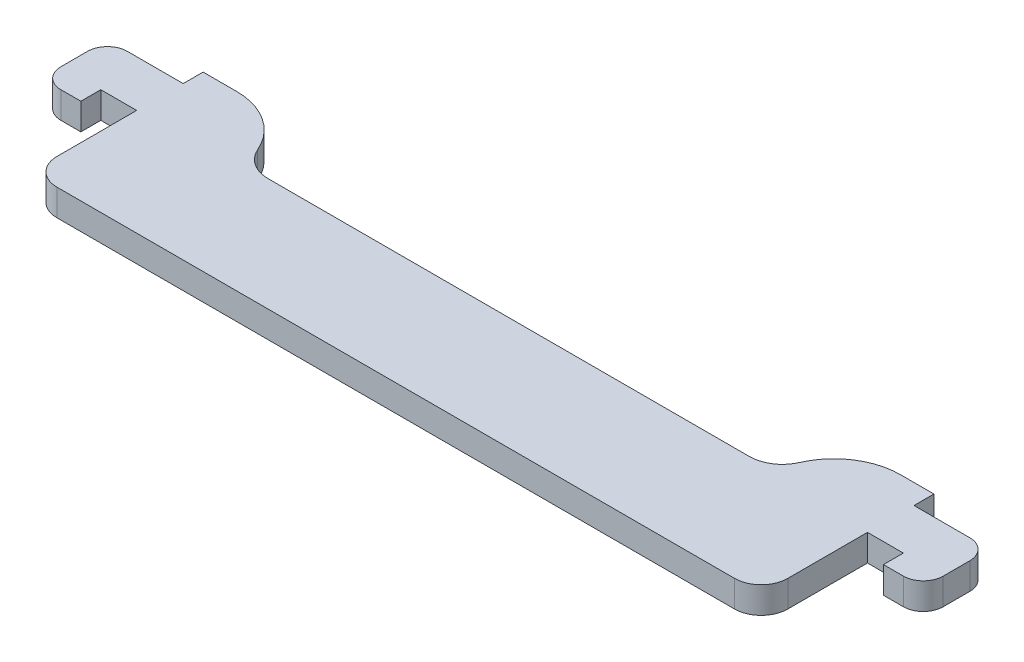
SolidWorks part; units mm, degrees
ref_plane "Piano frontale" through (0, 0, 0) normal (0, 0, 1) x (1, 0, 0)
ref_plane "Piano superiore" through (0, 0, 0) normal (0, 1, 0) x (1, 0, 0)
ref_plane "Piano destro" through (0, 0, 0) normal (1, 0, 0) x (0, 0, -1)
sketch "Schizzo1" plane through (0, 0, 0) normal (0, 1, 0) x (1, 0, 0)
  line L0 (-11.4, 23) -> (-11.4, 13)
  line L1 (-11.4, 13) -> (-5.4, 13)
  line L2 (-5.4, 13) -> (-5.4, 16)
  line L3 (-5.4, 16) -> (0, 16)
  line L4 (0, 16) -> (0, 0)
  line L5 (0, 0) -> (110, 0)
  line L6 (110, 0) -> (110, 16)
  line L7 (110, 16) -> (115.4, 16)
  line L8 (115.4, 16) -> (115.4, 13)
  line L9 (115.4, 13) -> (121.4, 13)
  line L10 (121.4, 13) -> (121.4, 23)
  line L11 (121.4, 23) -> (110, 23)
  line L12 (110, 23) -> (110, 26)
  line L13 (110, 26) -> (95, 26)
  line L14 (95, 26) -> (95, 17)
  line L19 (95, 17) -> (15, 17)
  line L20 (15, 17) -> (15, 26)
  line L21 (15, 26) -> (0, 26)
  line L22 (0, 26) -> (0, 23)
  line L23 (0, 23) -> (-11.4, 23)
  dimension "D1" = 10
  dimension "D2" = 6
  dimension "D3" = 6
  dimension "D4" = 5.4
  dimension "D5" = 5.4
  dimension "D6" = 15
  dimension "D7" = 15
  dimension "D8" = 17
  dimension "D9" = 3
  dimension "D10" = 3
  dimension "D11" = 16
  dimension "D13" = 110
extrude "Estrusione-Estrusione1" add sketch "Schizzo1" along normal blind 4
fillet "Raccordo1" radius 10 2 edges at (95, 2, -26) (15, 2, -26)
fillet "Raccordo2" radius 4 2 edges at (0, 2, 0) (110, 2, 0)
fillet "Raccordo9" radius 3 2 edges at (-11.4, 2, -13) (-11.4, 2, -23)
fillet "Raccordo10" radius 3 2 edges at (121.4, 2, -13) (121.4, 2, -23)
fillet "Raccordo11" radius 5 2 edges at (95, 2, -17) (15, 2, -17)
